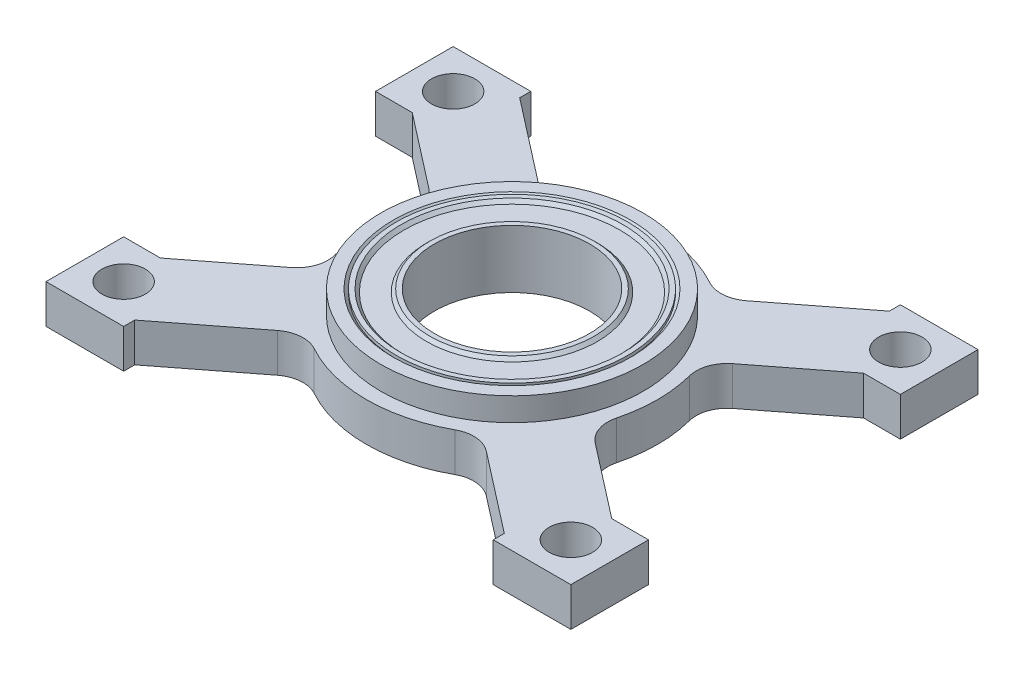
SolidWorks part; units mm, degrees
material "6061 Alloy"
ref_plane "Front Plane" through (0, 0, 0) normal (0, 0, 1) x (1, 0, 0)
ref_plane "Top Plane" through (0, 0, 0) normal (0, 1, 0) x (1, 0, 0)
ref_plane "Right Plane" through (0, 0, 0) normal (1, 0, 0) x (0, 0, -1)
sketch "Sketch1" plane through (0, 0, 0) normal (0, 1, 0) x (1, 0, 0)
  line L0 (-15.113, -16.6497) -> (-15.113, -15.7421)
  line L1 (-21.463, 16.6497) -> (-15.113, 16.6497)
  line L2 (-21.463, 16.6497) -> (-21.463, 10.2997)
  line L3 (-21.463, -16.6497) -> (-15.113, -16.6497)
  line L4 (21.463, 16.6497) -> (21.463, 10.2997)
  line L5 (-21.463, 16.6497) -> (-16.6105, 12.8854) construction
  line L6 (-21.463, -16.6497) -> (-16.6105, -12.8854) construction
  line L7 (15.113, -15.7421) -> (8.5372, -10.641)
  line L8 (15.113, -15.7421) -> (15.113, -16.6497)
  line L9 (15.113, -16.6497) -> (21.463, -16.6497)
  line L10 (-15.113, -15.7421) -> (-8.5372, -10.641)
  line L11 (-21.463, 0) -> (21.463, 0) construction
  line L12 (-15.113, 16.6497) -> (-15.113, 15.7421)
  line L13 (-15.113, 15.7421) -> (-8.5372, 10.641)
  line L14 (15.113, 15.7421) -> (15.113, 16.6497)
  line L15 (15.113, 15.7421) -> (8.5372, 10.641)
  line L16 (15.113, 16.6497) -> (21.463, 16.6497)
  line L17 (-21.463, -10.2997) -> (-21.463, -16.6497)
  line L18 (0, 16.6497) -> (0, -16.6497) construction
  line L19 (-12.4293, 5.6236) -> (-18.4572, 10.2997)
  line L20 (-21.463, 10.2997) -> (-18.4572, 10.2997)
  line L21 (-12.4293, -5.6236) -> (-18.4572, -10.2997)
  line L22 (-18.4572, -10.2997) -> (-21.463, -10.2997)
  line L23 (18.4572, -10.2997) -> (21.463, -10.2997)
  line L24 (12.4293, -5.6236) -> (18.4572, -10.2997)
  line L25 (21.463, 10.2997) -> (18.4572, 10.2997)
  line L26 (12.4293, 5.6236) -> (18.4572, 10.2997)
  line L27 (16.6105, -12.8854) -> (21.463, -16.6497) construction
  line L28 (-7.4758, -5.7993) -> (7.4758, 5.7993) construction
  line L29 (-7.4758, 5.7993) -> (7.4758, -5.7993) construction
  line L30 (16.6105, 12.8854) -> (21.463, 16.6497) construction
  line L31 (21.463, -10.2997) -> (21.463, -16.6497)
  circle A0 centre (0, 0) radius 9.4615
  arc A1 (11.5271, -2.9808) -> (11.5271, 2.9808) centre (0, 0) ccw
  circle A2 centre (-18.288, -13.4747) radius 1.778
  circle A3 centre (-18.288, 13.4747) radius 1.778
  circle A4 centre (18.288, -13.4747) radius 1.778
  circle A5 centre (18.288, 13.4747) radius 1.778
  arc A6 (-5.753, -10.4241) -> (5.753, -10.4241) centre (0, 0) ccw
  arc A7 (-11.5271, 2.9808) -> (-11.5271, -2.9808) centre (0, 0) ccw
  arc A8 (5.753, 10.4241) -> (-5.753, 10.4241) centre (0, 0) ccw
  arc A9 (-8.5372, 10.641) -> (-5.753, 10.4241) centre (-6.9803, 12.6479) ccw
  arc A10 (8.5372, 10.641) -> (5.753, 10.4241) centre (6.9803, 12.6479) cw
  arc A11 (12.4293, 5.6236) -> (11.5271, 2.9808) centre (13.9862, 3.6167) ccw
  arc A12 (12.4293, -5.6236) -> (11.5271, -2.9808) centre (13.9862, -3.6167) cw
  arc A13 (8.5372, -10.641) -> (5.753, -10.4241) centre (6.9803, -12.6479) ccw
  arc A14 (-8.5372, -10.641) -> (-5.753, -10.4241) centre (-6.9803, -12.6479) cw
  arc A15 (-12.4293, -5.6236) -> (-11.5271, -2.9808) centre (-13.9862, -3.6167) ccw
  arc A16 (-12.4293, 5.6236) -> (-11.5271, 2.9808) centre (-13.9862, 3.6167) cw
  point P53 (-7.1208, 9.5422)
  point P56 (7.1208, 9.5422)
  point P59 (11.0129, 4.5248)
  point P62 (11.0129, -4.5248)
  point P65 (7.1208, -9.5422)
  point P68 (-7.1208, -9.5422)
  point P71 (-11.0129, -4.5248)
  point P74 (-11.0129, 4.5248)
  dimension "D1" = 18.923
  dimension "D2" = 23.8125
  dimension "D11" = 3.556
  dimension "D12" = 18.288
  dimension "D14" = 2.54
  dimension "D3" = 33.2994
  dimension "D4" = 42.926
  dimension "D5" = 30.226
  dimension "D6" = 15.113
  dimension "D7" = 3.175
  dimension "D8" = 3.175
  dimension "D9" = 20.5994
  dimension "D10" = 3.175
  dimension "D13" = 13.4747
extrude "Boss-Extrude1" add sketch "Sketch1" along normal blind 3.175 contours L15 A8 L13 L12 L1 L2 L20 L19 A7 L21 L22 L17 L3 L0 L10 A6 L7 L8 L9 L4 L23 L24 A1 L26 L25 L16 L14 A4 A0 A2 A3 A5 region at (-18.288, 0, 16.1064)
sketch "Sketch2" plane through (0, 3.175, 0) normal (0, 1, 0) x (1, 0, 0)
  circle A0 centre (0, 0) radius 9.4615
  circle A1 centre (0, 0) radius 10.7315
  dimension "D1" = 21.463
  dimension "D2" = 18.923
extrude "Boss-Extrude2" add sketch "Sketch2" along normal blind 1.905
chamfer "Chamfer1" distance 0.254 angle 45 2 edges at (0, 0, 9.4615) (0, 5.08, 9.4615)
sketch "Sketch3" plane through (0, 5.08, 0) normal (0, 1, 0) x (1, 0, 0)
  circle A0 centre (0, 0) radius 9.4615
  circle A1 centre (0, 0) radius 8.8265
  dimension "D1" = 0.635
extrude "Boss-Extrude3" add sketch "Sketch3" against normal blind 4.7625 separate body
chamfer "Chamfer2" distance 0.254 angle 45 2 edges at (0, 5.08, 8.8265) (0, 0.3175, 8.8265)
ref_plane "Plane1" through (0, 4.826, 0) normal (0, 1, 0) x (-1, 0, 0)
sketch "Sketch4" plane through (0, 4.826, 0) normal (0, 1, 0) x (-1, 0, 0)
  circle A0 centre (0, 0) radius 8.8265
  circle A1 centre (0, 0) radius 6.35 construction
  circle A2 centre (0, 0) radius 6.985
  dimension "D1" = 0.635
extrude "Boss-Extrude4" add sketch "Sketch4" against normal blind 4.2545
sketch "Sketch5" plane through (0, 5.08, 0) normal (0, 1, 0) x (1, 0, 0)
  circle A0 centre (0, 0) radius 6.985
  circle A1 centre (0, 0) radius 6.35
  dimension "D1" = 12.7
extrude "Boss-Extrude5" add sketch "Sketch5" against normal blind 4.7625
chamfer "Chamfer3" distance 0.254 angle 45 2 edges at (0, 0.3175, 6.985) (0, 5.08, 6.985)
